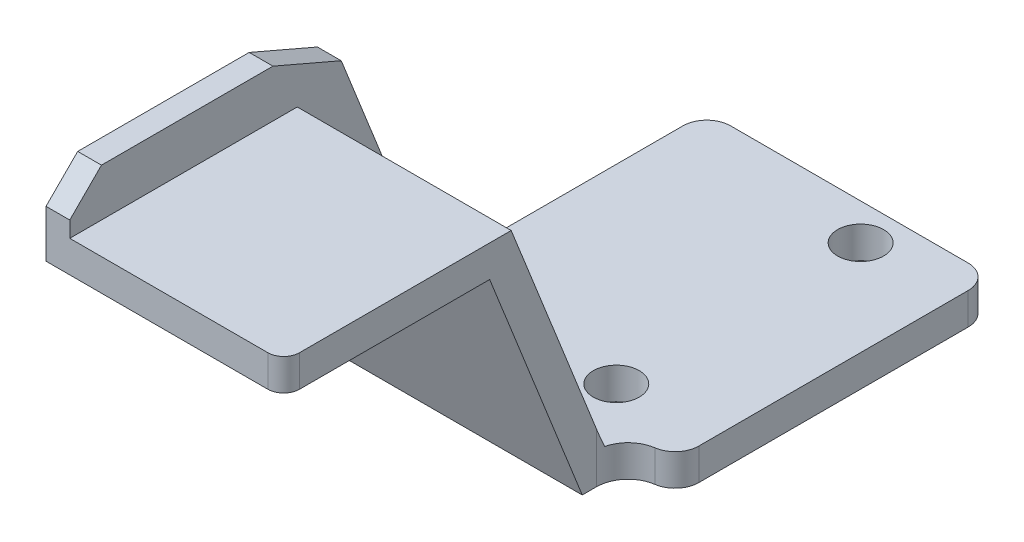
SolidWorks part; units mm, degrees
ref_plane "Front Plane" through (0, 0, 0) normal (0, 0, 1) x (1, 0, 0)
ref_plane "Top Plane" through (0, 0, 0) normal (0, 1, 0) x (1, 0, 0)
ref_plane "Right Plane" through (0, 0, 0) normal (1, 0, 0) x (0, 0, -1)
sketch "Sketch1" plane through (0, 0, 0) normal (0, 1, 0) x (1, 0, 0)
  line L0 (3, 7.71) -> (3, -7.71) construction
  line L1 (9, 10) -> (-9, 10)
  line L2 (9, 10) -> (9, -10)
  line L3 (9, -10) -> (-9, -10)
  line L4 (-9, 10) -> (-9, -10)
  line L5 (9, 10) -> (-9, -10) construction
  line L6 (9, -10) -> (-9, 10) construction
  circle A0 centre (3, 7.71) radius 1.45
  circle A1 centre (3, -7.71) radius 1.45
  point P0 (0, 0)
  point P8 (3, 0)
  dimension "D3" = 6
  dimension "D5" = 2.9
  dimension "D1" = 20
  dimension "D2" = 15.42
  dimension "D4" = 12
extrude "Boss-Extrude1" add sketch "Sketch1" along normal blind 2
sketch "Sketch2" plane through (-9, 0, 0) normal (-1, 0, 0) x (0, 0, 1)
  line L0 (10, 2) -> (11.5, 2)
  line L1 (11.5, 2) -> (17.3427, 16.7)
  line L2 (17.3427, 16.7) -> (31.7, 16.7)
  line L3 (10, 0) -> (12.8573, 0)
  line L4 (12.8573, 0) -> (18.7, 14.7)
  line L5 (18.7, 14.7) -> (31.7, 14.7)
  line L6 (31.7, 14.7) -> (31.7, 16.7)
  line L9 (-10, 0) -> (10, 0) construction
  line L10 (10, 2) -> (10, 0)
  dimension "D1" = 14.7
  dimension "D2" = 2
  dimension "D3" = 8.7
  dimension "D4" = 13
  dimension "D5" = 1.5
  dimension "D6" = 2
extrude "Boss-Extrude2" add sketch "Sketch2" against normal blind 15
sketch "Sketch4" plane through (-9, 0, 0) normal (-1, 0, 0) x (0, 0, 1)
  line L0 (31.7, 16.7) -> (17.3427, 16.7) construction
  line L1 (17.3427, 16.7) -> (11.5, 2) construction
  line L2 (31.7, 16.7) -> (17.3427, 16.7)
  line L3 (17.3427, 16.7) -> (11.5, 2)
  line L6 (31.7, 19.7) -> (15.3069, 19.7)
  line L7 (15.3069, 19.7) -> (11.5, 10.1222)
  line L9 (31.7, 16.7) -> (31.7, 19.7)
  line L11 (3.7672, 29.5774) -> (11.5, 10.1222) construction
  line L12 (0.9794, 28.4693) -> (11.5, 2) construction
  line L13 (11.5, 10.1222) -> (11.5, 2)
  dimension "D1" = 3
extrude "Boss-Extrude4" add sketch "Sketch4" against normal blind 1.5
chamfer "Chamfer1" distance 2 angle 45 2 edges at (-8.25, 19.7, 31.7) (-8.25, 19.7, 15.3069)
fillet "Fillet1" radius 1.5 3 edges at (9, 1, 10) (9, 1, -10) (-9, 1, -10)
fillet "Fillet2" radius 1 1 edges at (6, 15.7, 31.7)
fillet "Fillet3" radius 2 1 edges at (6, 1, 10)
sketch "Sketch5" plane through (-9, 0, 0) normal (-1, 0, 0) x (0, 0, 1)
  line L0 (-8.5, 2) -> (11.5, 2) construction
  line L1 (11.5, 10.1222) -> (11.5, 2) construction
  line L2 (10, 2) -> (11.5, 2)
  line L3 (11.5, 2) -> (11.5, 3.5)
  arc A0 (10, 2) -> (11.5, 3.5) centre (10, 3.5) ccw
  dimension "D1" = 1.5
extrude "Fillet" add sketch "Sketch5" against normal up to surface (1.5 mm away) up to face at (-7.5, 15.0579, 20.8612)
